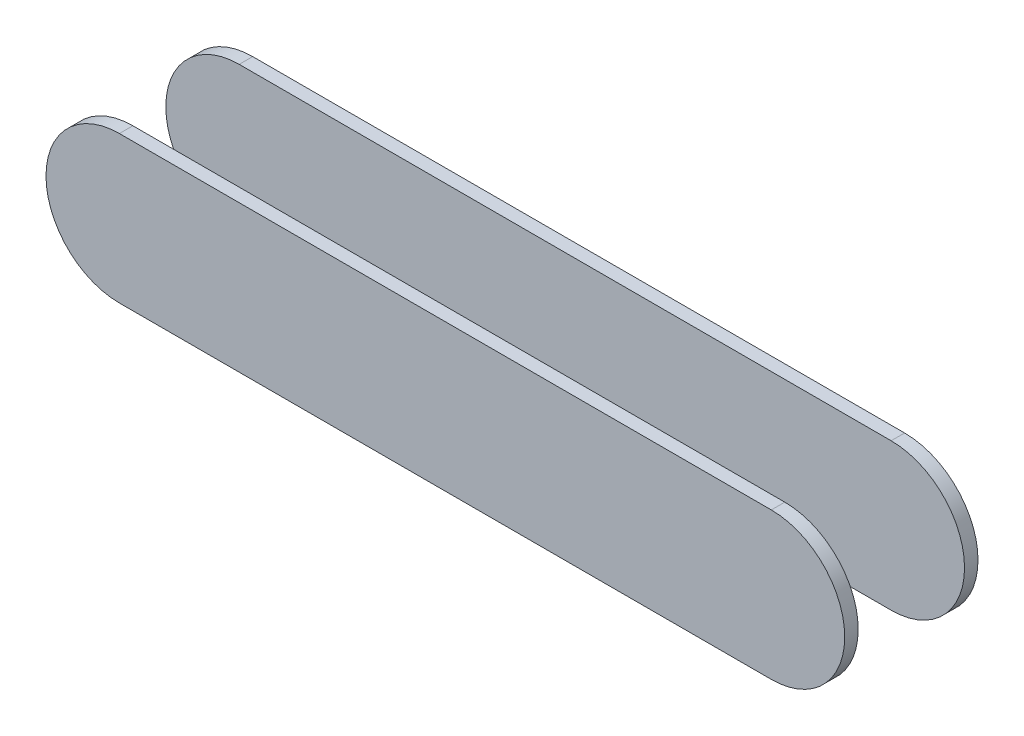
SolidWorks part; units mm, degrees
ref_plane "Front Plane" through (0, 0, 0) normal (0, 0, 1) x (1, 0, 0)
ref_plane "Top Plane" through (0, 0, 0) normal (0, 1, 0) x (1, 0, 0)
ref_plane "Right Plane" through (0, 0, 0) normal (1, 0, 0) x (0, 0, -1)
sketch "Sketch1" plane through (0, 0, 0) normal (0, 0, 1) x (1, 0, 0)
  line L0 (0, 25.9485) -> (230.49, 25.9485)
  line L1 (0, -25.9485) -> (230.49, -25.9485)
  line L2 (0, 25.9485) -> (0, -25.9485)
  line L3 (230.49, 25.9485) -> (230.49, -25.9485)
  arc A0 (0, 25.9485) -> (0, -25.9485) centre (0, 0) ccw
  arc A1 (230.49, -25.9485) -> (230.49, 25.9485) centre (230.49, 0) ccw
  dimension "D1" = 230.49
extrude "Boss-Extrude1" add sketch "Sketch1" along normal blind 4.7625 contours L3 L0 L2 L1 | L2 A0 | L3 A1 region at (115.245, 0, 0) region at (-11.0129, 0, 0) region at (241.5029, 0, 0)
ref_plane "Plane1" through (0, 0, 42.3625) normal (0, 0, 1) x (1, 0, 0)
sketch "Sketch2" plane through (0, 0, 42.3625) normal (0, 0, 1) x (1, 0, 0)
  line L0 (0, 25.9485) -> (230.49, 25.9485)
  line L1 (0, -25.9485) -> (230.49, -25.9485)
  arc A0 (0, 25.9485) -> (0, -25.9485) centre (0, 0) ccw
  arc A1 (230.49, -25.9485) -> (230.49, 25.9485) centre (230.49, 0) ccw
extrude "Boss-Extrude2" add sketch "Sketch2" along normal blind 4.7625 separate body
